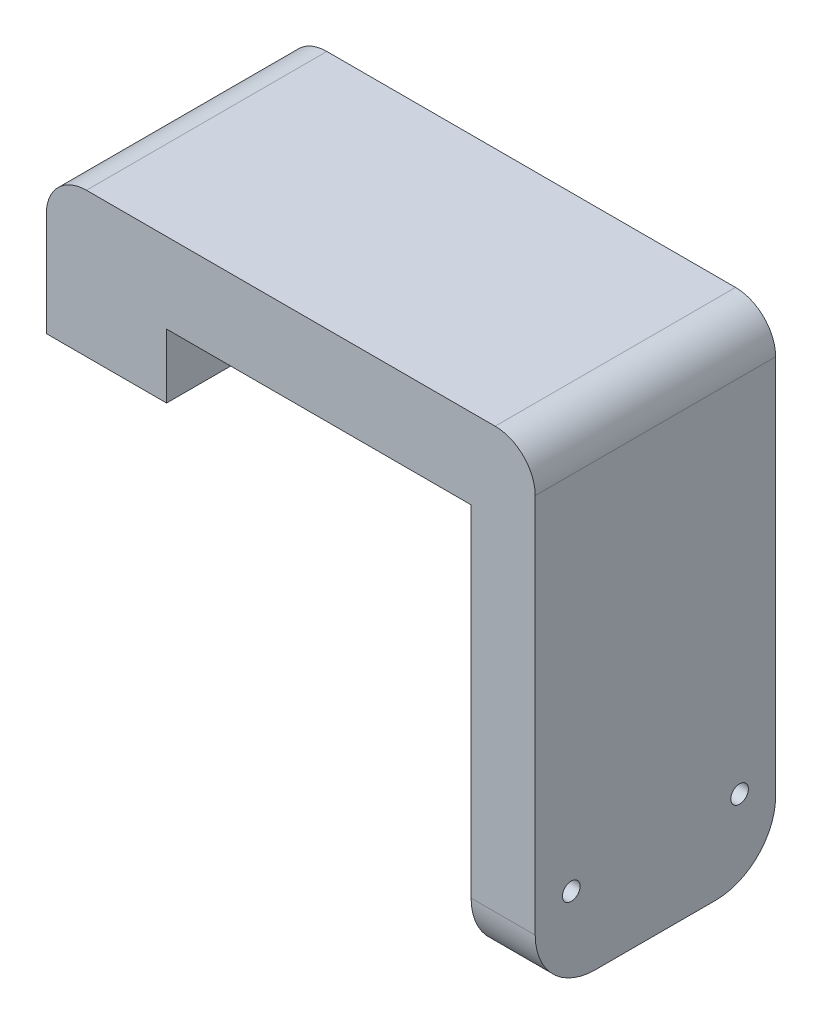
SolidWorks part; units mm, degrees
material "ABS"
ref_plane "正面" through (0, 0, 0) normal (0, 0, 1) x (1, 0, 0)
ref_plane "平面" through (0, 0, 0) normal (0, 1, 0) x (1, 0, 0)
ref_plane "右側面" through (0, 0, 0) normal (1, 0, 0) x (0, 0, -1)
sketch "ｽｹｯﾁ1" plane through (0, 0, 0) normal (0, 0, 1) x (1, 0, 0)
  line L0 (0, 0) -> (-15, 0)
  line L1 (-15, 0) -> (-15, 13)
  line L2 (-10, 18) -> (41, 18)
  line L3 (46, 13) -> (46, -42)
  line L4 (46, -42) -> (38, -42)
  line L5 (0, 0) -> (0, 8)
  line L6 (0, 8) -> (38, 8)
  line L7 (38, 8) -> (38, -42)
  line L9 (36.845, 7.339) -> (0.845, 7.339)
  line L10 (36.845, 7.339) -> (36.845, -28.661) construction
  line L11 (36.845, -28.661) -> (0.845, -28.661) construction
  line L12 (0.845, 7.339) -> (0.845, -28.661) construction
  arc A0 (41, 18) -> (46, 13) centre (41, 13) cw
  arc A1 (-15, 13) -> (-10, 18) centre (-10, 13) cw
  point P12 (46, 18)
  dimension "D7" = 5
  dimension "D1" = 38
  dimension "D2" = 60
  dimension "D3" = 8
  dimension "D4" = 10
  dimension "D5" = 15
  dimension "D6" = 8
  dimension "D8" = 36
extrude "ﾎﾞｽ - 押し出し1" add sketch "ｽｹｯﾁ1" along normal blind 30 contours A1 L1 L0 L5 L6 L7 L4 L3 A0 L2 region at (-7.5, 0.8556, 0)
sketch "ｽｹｯﾁ2" plane through (38, 0, 0) normal (-1, 0, 0) x (0, 0, 1)
  line L0 (0, -32) -> (30, -32) construction
  line L3 (30, -42) -> (0, -42) construction
  line L4 (30, 8) -> (30, -42) construction
  circle A0 centre (4.5, -32) radius 1.1
  circle A1 centre (25.5, -32) radius 1.1
  point P2 (30, -32)
  point P4 (0, 0)
  point P12 (0, 0)
  dimension "D1" = 21
  dimension "D3" = 2.2
  dimension "D2" = 4.5
  dimension "D4" = 10
extrude "ｶｯﾄ - 押し出し1" cut sketch "ｽｹｯﾁ2" against normal through all
fillet "ﾌｨﾚｯﾄ1" radius 7.5 2 edges at (42, -42, 30) (42, -42, 0)
